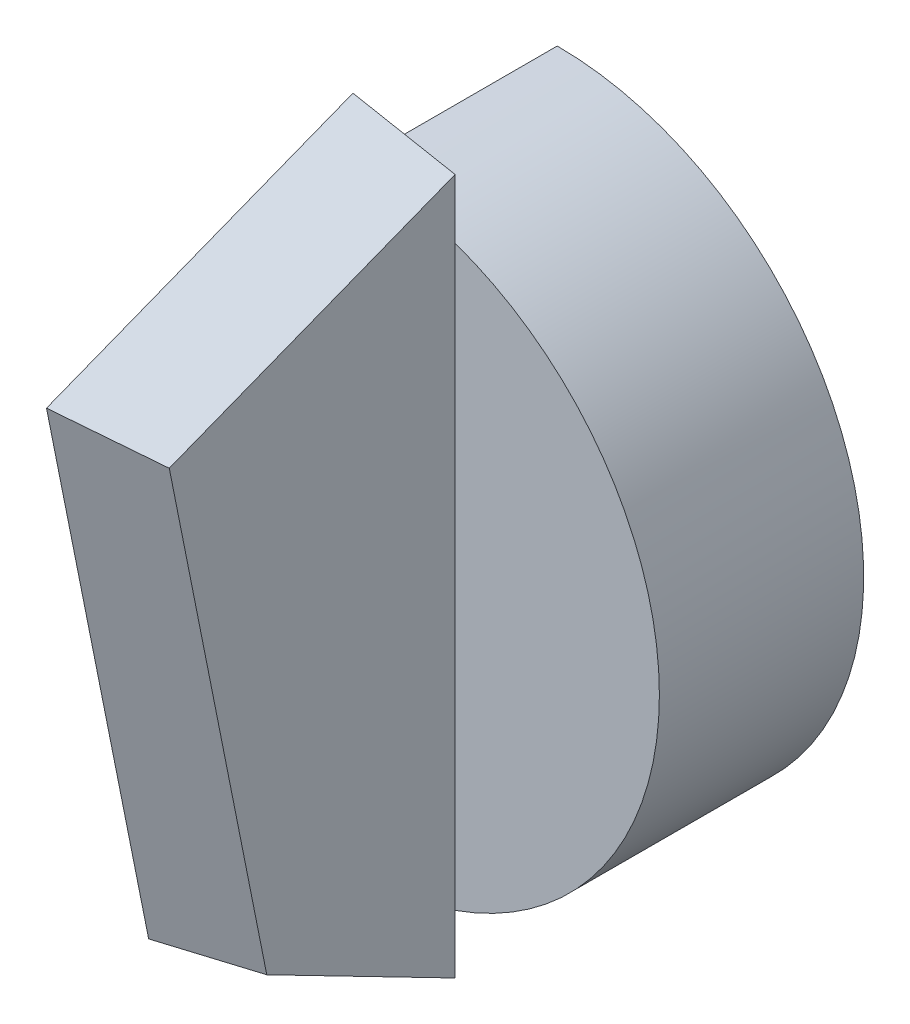
SolidWorks part; units mm, degrees
ref_plane "Front Plane" through (0, 0, 0) normal (0, 0, 1) x (1, 0, 0)
ref_plane "Top Plane" through (0, 0, 0) normal (0, 1, 0) x (1, 0, 0)
ref_plane "Right Plane" through (0, 0, 0) normal (1, 0, 0) x (0, 0, -1)
sketch "Sketch1" plane through (0, 0, 0) normal (0, 0, 1) x (1, 0, 0)
  line L0 (0, 15) -> (0, -15)
  arc A1 (0, -15) -> (0, 15) centre (0, 0) ccw
  dimension "D1" = 15
extrude "Boss-Extrude1" add sketch "Sketch1" along normal blind 10 contours A1 L0
sketch "Sketch3" plane through (0, 0, 0) normal (1, 0, 0) x (0, 0, -1)
  line L4 (-10, 18) -> (-10, -18)
  line L5 (-10, -18) -> (-20, -12.8513)
  line L7 (-25, 12.1487) -> (-10, 18)
  line L8 (-10, 15) -> (-10, -15) construction
  line L9 (-25, 12.1487) -> (-20, -12.8513)
  point P4 (-25, 12.4749)
  point P7 (0, 0)
  point P9 (0, 0)
  point P10 (0, 0)
  point P11 (-24.9975, 17.4181)
  dimension "D1" = 18
  dimension "D2" = 10
  dimension "D3" = 15
  dimension "D4" = 25
  dimension "D5" = 18
  dimension "D6" = 100
extrude "Boss-Extrude2" add sketch "Sketch3" along normal blind 5 contours L9 L5 L4 L7
draft "Draft1" type of draft neutral plane draft angle 10 neutral plane "Right Plane" faces to draft 3 face at (2.5, 15.0744, 17.5) face at (2.5, -0.3513, 22.5) face at (2.5, -15.4256, 15) neutral plane through (0, 0, 0) neutral plane normal (1, 0, 0) parameters "D1"=10
